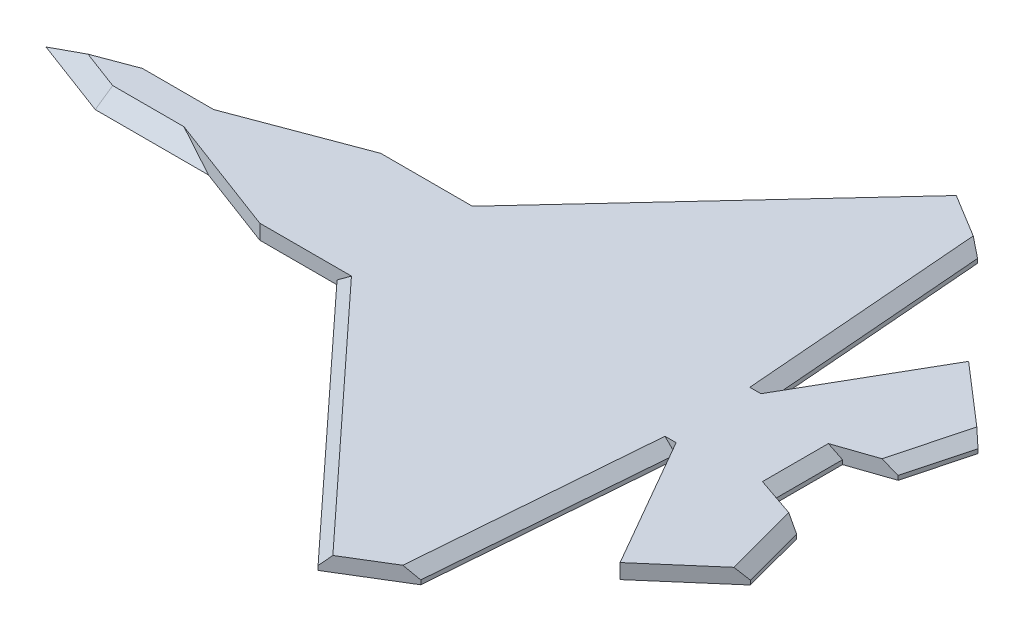
SolidWorks part; units mm, degrees
ref_plane "Front Plane" through (0, 0, 0) normal (0, 0, 1) x (1, 0, 0)
ref_plane "Top Plane" through (0, 0, 0) normal (0, 1, 0) x (1, 0, 0)
ref_plane "Right Plane" through (0, 0, 0) normal (1, 0, 0) x (0, 0, -1)
sketch "Sketch1" plane through (0, 0, 0) normal (0, 1, 0) x (1, 0, 0)
  line L0 (0.2842, 0.0487) -> (70, 0.0487) construction
  line L28 (0.2842, 0.0487) -> (4.8222, 1.7529)
  line L29 (0.2842, 0.0487) -> (4.8222, -1.6554)
  line L30 (4.8222, 1.7529) -> (11.041, 1.7529)
  line L31 (4.8222, -1.6554) -> (11.041, -1.6554)
  line L32 (11.041, 1.7529) -> (14.1371, 2.9155)
  line L33 (11.041, -1.6554) -> (14.1371, -2.818)
  line L34 (14.1371, 2.9155) -> (17.7987, 2.9155)
  line L35 (14.1371, -2.818) -> (17.7987, -2.818)
  line L36 (17.7987, 2.9155) -> (29.0708, 15.0874)
  line L37 (17.7987, -2.818) -> (29.0708, -14.9899)
  line L38 (29.0708, 15.0874) -> (32.0942, 13.2441)
  line L39 (29.0708, -14.9899) -> (32.0942, -13.1466)
  line L40 (32.0942, 13.2441) -> (32.9867, 2.0587)
  line L41 (32.0942, -13.1466) -> (32.9867, -1.9612)
  line L42 (32.9867, 2.0587) -> (33.0115, 2.0587)
  line L43 (32.9867, -1.9612) -> (33.0115, -1.9612)
  line L44 (33.0115, 2.0587) -> (36.6051, 8.307)
  line L45 (33.0115, -1.9612) -> (36.6051, -8.2095)
  line L46 (36.6051, 8.307) -> (39.9165, 5.4419)
  line L47 (36.6051, -8.2095) -> (39.9165, -5.3444)
  line L48 (39.9165, 5.4419) -> (39.1176, 2.4538)
  line L49 (39.9165, -5.3444) -> (39.1176, -2.3563)
  line L50 (39.1176, 2.4538) -> (37.1559, 1.7816)
  line L51 (39.1176, -2.3563) -> (37.1559, -1.6841)
  line L52 (37.1559, 1.7816) -> (37.1559, -1.6841)
  point P27 (37.1559, 0.0487)
extrude "Boss-Extrude1" add sketch "Sketch1" along normal blind 0.7
chamfer "Chamfer1" distance 1 angle 45 4 edges at (7.9316, 0.7, -1.7529) (2.5532, 0.7, -0.9008) (7.9316, 0.7, 1.6554) (2.5532, 0.7, 0.8033)
chamfer "Chamfer2" distance 0.5 angle 45 7 edges at (32.5404, 0.7, -7.6514) (23.4347, 0.7, -9.0015) (23.4347, 0.7, 8.904) (32.5404, 0.7, 7.5539) (37.1559, 0.7, -0.0487) (39.517, 0.7, 3.8504) (39.517, 0.7, -3.9479)
sketch "Sketch6" plane through (0, 0.7, 0) normal (0, 1, 0) x (1, 0, 0)
  line L0 (6.6763, 0.4956) -> (6.8504, 0.4956)
  line L1 (-0.8473, 0) -> (0.8473, 0) construction
  line L2 (6.6763, -0.4956) -> (6.8504, -0.4956)
  arc A0 (6.6763, 0.4956) -> (6.8504, 0.4956) centre (6.7634, -0.8632) cw
  arc A2 (6.6763, -0.4956) -> (6.8504, -0.4956) centre (6.7634, 0.8632) ccw
sketch "Sketch7" plane through (0, 0, 0) normal (0, 0, 1) x (1, 0, 0)
  line L0 (4.8653, 0.6176) -> (9.1672, 0.6176)
  spline S0 degree 3 poles (4.8653, 0.6176) (5.0176, 1.0806) (5.4153, 2.2905) (7.509, 1.2845) (8.6331, 0.8324) (9.1672, 0.6176) knots 0 0 0 0 0.245531 0.641509 1 1 1 1
ref_plane "Plane1" through (7, 0, 0) normal (1, 0, 0) x (0, 0, -1)
